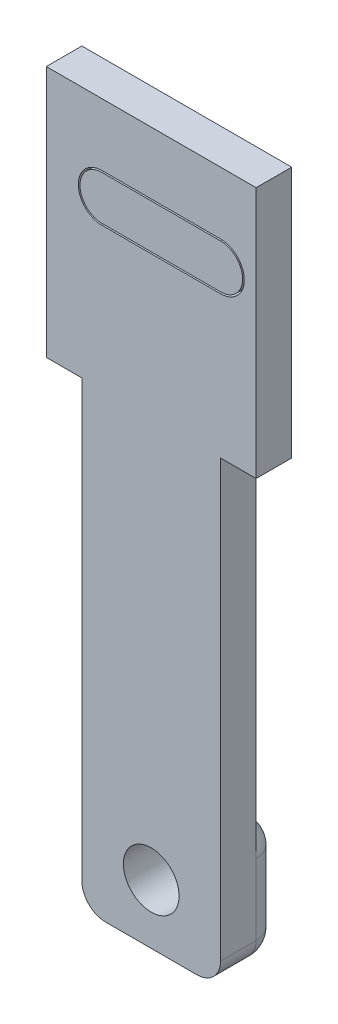
SolidWorks part; units mm, degrees
ref_plane "Front Plane" through (0, 0, 0) normal (0, 0, 1) x (1, 0, 0)
ref_plane "Top Plane" through (0, 0, 0) normal (0, 1, 0) x (1, 0, 0)
ref_plane "Right Plane" through (0, 0, 0) normal (1, 0, 0) x (0, 0, -1)
sketch "Sketch1" plane through (0, 0, 0) normal (0, 0, 1) x (1, 0, 0)
  line L1 (-43.4143, 34.026) -> (-25.7143, 34.026)
  line L2 (-43.4143, 34.026) -> (-43.4143, -25.974)
  line L3 (-43.4143, -25.974) -> (-25.7143, -25.974)
  line L4 (-25.7143, 34.026) -> (-25.7143, -25.974)
  dimension "D1" = 17.7
  dimension "D2" = 60
extrude "Boss-Extrude1" add sketch "Sketch1" along normal blind 3
sketch "Sketch2" plane through (0, 0, 3) normal (0, 0, 1) x (1, 0, 0)
  line L1 (-43.4143, -25.974) -> (-40.4143, -25.974)
  line L2 (-43.4143, -25.974) -> (-43.4143, 12.776)
  line L3 (-43.4143, 12.776) -> (-40.4143, 12.776)
  line L4 (-40.4143, -25.974) -> (-40.4143, 12.776)
  line L5 (-25.7143, -25.974) -> (-28.7143, -25.974)
  line L6 (-25.7143, -25.974) -> (-25.7143, 12.776)
  line L7 (-25.7143, 12.776) -> (-28.7143, 12.776)
  line L8 (-28.7143, -25.974) -> (-28.7143, 12.776)
  dimension "D1" = 38.75
  dimension "D2" = 38.75
  dimension "D3" = 3
  dimension "D4" = 3
extrude "Cut-Extrude1" cut sketch "Sketch2" against normal through all
sketch "Sketch3" plane through (0, 0, 3) normal (0, 0, 1) x (1, 0, 0)
  line L0 (-28.7143, 26.776) -> (-38.7143, 26.776) construction
  line L1 (-28.7143, 25.526) -> (-38.7143, 25.526)
  line L2 (-28.7143, 28.026) -> (-38.7143, 28.026)
  line L3 (-25.7143, 34.026) -> (-43.4143, 34.026) construction
  line L4 (-25.7143, 12.776) -> (-25.7143, 34.026) construction
  arc A0 (-28.7143, 25.526) -> (-28.7143, 28.026) centre (-28.7143, 26.776) ccw
  arc A1 (-38.7143, 28.026) -> (-38.7143, 25.526) centre (-38.7143, 26.776) ccw
  point P2 (-33.7143, 26.776)
  dimension "D3" = 3
  dimension "D1" = 6
  dimension "D2" = 2.5
  dimension "D4" = 10
extrude "Cut-Extrude2" cut sketch "Sketch3" against normal through all
sketch "Sketch4" plane through (0, 0, 3) normal (0, 0, 1) x (1, 0, 0)
  line L0 (-38.7143, 26.776) -> (-28.7143, 26.776) construction
  line L1 (-38.7143, 28.776) -> (-28.7143, 28.776)
  line L2 (-38.7143, 24.776) -> (-28.7143, 24.776)
  arc A0 (-38.7143, 28.776) -> (-38.7143, 24.776) centre (-38.7143, 26.776) ccw
  arc A1 (-28.7143, 24.776) -> (-28.7143, 28.776) centre (-28.7143, 26.776) ccw
  point P4 (-33.7143, 26.776)
  dimension "D1" = 4
extrude "Cut-Extrude3" cut sketch "Sketch4" against normal blind 2
sketch "Sketch5" plane through (0, 0, 0) normal (0, 0, -1) x (-1, 0, 0)
  line L0 (40.4143, -25.974) -> (40.4143, 12.776) construction
  line L1 (28.7143, -25.974) -> (40.4143, -25.974)
  line L2 (28.7143, -25.974) -> (28.7143, -15.974)
  line L3 (28.7143, -15.974) -> (40.4143, -15.974)
  line L4 (40.4143, -25.974) -> (40.4143, -15.974)
  dimension "D1" = 10
extrude "Boss-Extrude2" add sketch "Sketch5" along normal blind 2
sketch "Sketch6" plane through (0, 0, -2) normal (0, 0, -1) x (-1, 0, 0)
  line L0 (28.7143, -25.974) -> (40.4143, -25.974) construction
  circle A0 centre (34.5643, -20.974) radius 2.35
  dimension "D1" = 4.7
  dimension "D2" = 5
extrude "Cut-Extrude4" cut sketch "Sketch6" against normal through all both and the other way through all
fillet "Fillet1" radius 2 1 edges at (-34.5643, -25.974, -2)
fillet "Fillet2" radius 2 1 edges at (-34.5643, -15.974, -2)
fillet "Fillet3" radius 2 4 edges at (-28.7143, -16.5598, -1.4142) (-28.7143, -20.974, -2) (-28.7143, -25.3882, -1.4142) (-28.7143, -25.974, 1.5)
fillet "Fillet4" radius 2 4 edges at (-40.4143, -16.5598, -1.4142) (-40.4143, -20.974, -2) (-40.4143, -25.3882, -1.4142) (-40.4143, -25.974, 1.5)
sketch "Sketch7" plane through (0, 0, 3) normal (0, 0, 1) x (1, 0, 0)
  line L0 (-28.7143, 26.776) -> (-38.7143, 26.776) construction
  line L1 (-28.7143, 24.9143) -> (-38.7143, 24.9143)
  line L2 (-28.7143, 28.6377) -> (-38.7143, 28.6377)
  arc A0 (-28.7143, 24.9143) -> (-28.7143, 28.6377) centre (-28.7143, 26.776) ccw
  arc A1 (-38.7143, 28.6377) -> (-38.7143, 24.9143) centre (-38.7143, 26.776) ccw
  point P4 (-33.7143, 26.776)
extrude "Boss-Extrude3" add sketch "Sketch7" against normal blind 1.75 separate body
